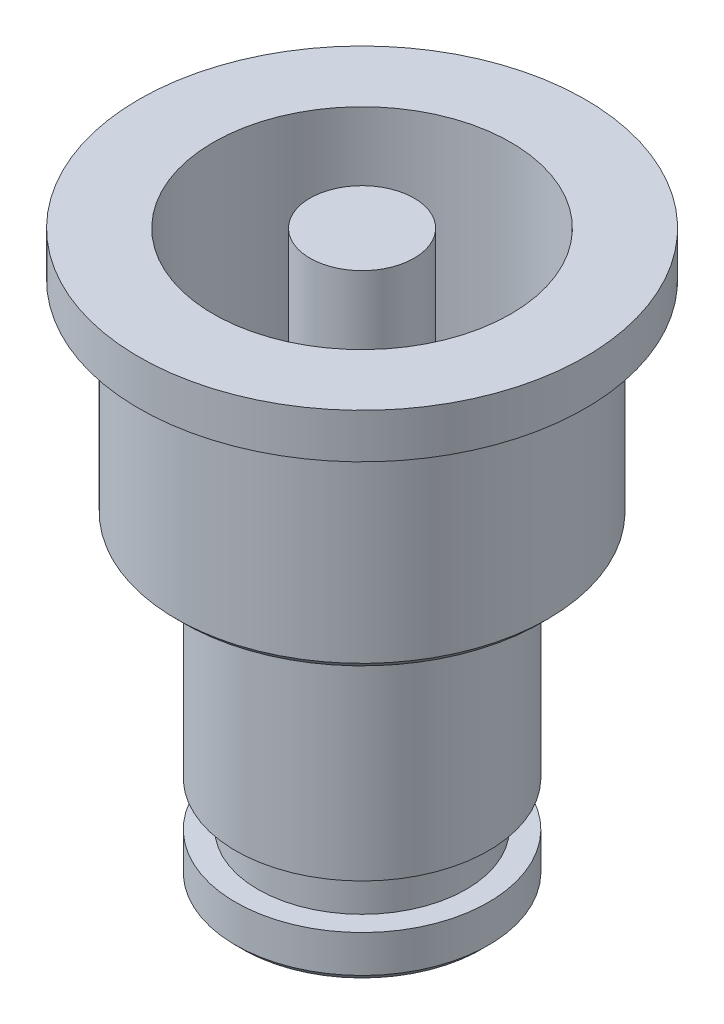
SolidWorks part; units mm, degrees
ref_plane "Plan de face" through (0, 0, 0) normal (0, 0, 1) x (1, 0, 0)
ref_plane "Plan de dessus" through (0, 0, 0) normal (0, 1, 0) x (1, 0, 0)
ref_plane "Plan de droite" through (0, 0, 0) normal (1, 0, 0) x (0, 0, -1)
sketch "Sketch1" plane through (0, 0, 0) normal (0, 1, 0) x (1, 0, 0)
  line L1 (0, 8) -> (-88, 8)
  line L2 (0, 8) -> (0, -8)
  line L3 (0, -8) -> (-88, -8)
  line L4 (-88, 8) -> (-88, -8)
  line L5 (-85, 6.25) -> (-62, 6.25)
  line L6 (-85, 6.25) -> (-85, -6.25)
  line L7 (-85, -6.25) -> (-62, -6.25)
  line L8 (-62, 6.25) -> (-62, -6.25)
  line L9 (-85, 6.25) -> (-62, -6.25) construction
  line L10 (-85, -6.25) -> (-62, 6.25) construction
  point P4 (0, 0)
  point P6 (-73.5, 0)
  dimension "D1" = 88
  dimension "D2" = 16
  dimension "D3" = 3
  dimension "D4" = 23
  dimension "D5" = 12.5
extrude "Boss-Extrude1" add sketch "Sketch1" along normal blind 5
sketch "Sketch2" plane through (0, 0, 0) normal (0, -1, 0) x (1, 0, 0)
  circle A0 centre (0, 0) radius 8
extrude "Boss-Extrude2" add sketch "Sketch2" along normal blind 5 and the other way up to surface (5 mm away) other way up to face at (-44, 5, 0)
fillet "Fillet1" radius 2 1 edges at (-8, 0, 0)
sketch "Sketch11" plane through (0, 0, 0) normal (0, 0, 1) x (1, 0, 0)
  line L0 (0, -5) -> (0, -43) construction
  line L1 (-8, -5) -> (8, -5) construction
  line L2 (0, -5) -> (15, -5)
  line L3 (15, -5) -> (15, -8)
  line L4 (15, -8) -> (12.5, -8)
  line L5 (12.5, -8) -> (12.5, -22)
  line L6 (12.5, -22) -> (8.5, -22)
  line L7 (8.5, -22) -> (8.5, -37)
  line L8 (8.5, -37) -> (7, -37)
  line L9 (7, -37) -> (7, -40)
  line L10 (7, -40) -> (8.5, -40)
  line L11 (8.5, -40) -> (8.5, -43)
  line L12 (8.5, -43) -> (0, -43)
  line L14 (0, -5) -> (0, -43)
  dimension "D1" = 30
  dimension "D2" = 25
  dimension "D3" = 3
  dimension "D4" = 14
  dimension "D5" = 17
  dimension "D6" = 21
  dimension "D7" = 3
  dimension "D8" = 3
  dimension "D9" = 14
  dimension "D10" = 17
revolve "Revolve1" add sketch "Sketch11" angle 360 about L0
chamfer "Chamfer1" distance 0.5 angle 45 2 edges at (-8.5, -43, 0) (-12.5, -22, 0)
sketch "Sketch5" plane through (0, -43, 0) normal (0, -1, 0) x (1, 0, 0)
  line L0 (-1.45, 2.569) -> (-1.45, -2.569)
  line L1 (1.45, 2.569) -> (1.45, -2.569)
  arc A0 (-1.45, -2.569) -> (1.45, -2.569) centre (0, 0) ccw
  arc A1 (1.45, 2.569) -> (-1.45, 2.569) centre (0, 0) ccw
  dimension "D1" = 5.9
  dimension "D2" = 1.45
  dimension "D3" = 1.45
extrude "Cut-Extrude1" cut sketch "Sketch5" against normal blind 8
sketch "Sketch6" plane through (0, 5, 0) normal (0, 1, 0) x (1, 0, 0)
  line L0 (-62, -6.25) -> (-62, 6.25) construction
  line L1 (-62, -3) -> (-59, -3)
  line L2 (-62, -3) -> (-62, 3)
  line L3 (-62, 3) -> (-59, 3)
  line L4 (-59, -3) -> (-59, 3)
  line L7 (-56, 3) -> (-12, 3)
  line L8 (-56, 3) -> (-56, -3)
  line L9 (-56, -3) -> (-12, -3)
  line L10 (-12, 3) -> (-12, -3)
  point P6 (-62, 0)
  point P7 (-62, 0)
  dimension "D1" = 6
  dimension "D2" = 3
  dimension "D3" = 50
  dimension "D4" = 3
extrude "Cut-Extrude2" cut sketch "Sketch6" against normal up to surface (5 mm away) up to face at (-48, 0, 0)
chamfer "Chamfer2" distance 0.5 angle 45 5 edges at (-62, 5, -4.625) (-62, 5, 4.625) (-73.5, 5, 6.25) (-85, 5, 0) (-73.5, 5, -6.25)
shell "Shell1" [suppressed] thickness 2
sketch "Sketch12" plane through (0, 0, 0) normal (0, 0, 1) x (1, 0, 0)
  line L0 (15, -5) -> (-15, -5) construction
  line L1 (9.1233, -5) -> (-100.7586, -5)
  line L2 (9.1233, -5) -> (9.1233, 7.135)
  line L3 (9.1233, 7.135) -> (-100.7586, 7.135)
  line L4 (-100.7586, -5) -> (-100.7586, 7.135)
extrude "Cut-Extrude3" cut sketch "Sketch12" against normal through all both and the other way through all
sketch "Sketch13" plane through (0, -5, 0) normal (0, 1, 0) x (1, 0, 0)
  circle A0 centre (0, 0) radius 10
  circle A2 centre (0, 0) radius 3.5
  dimension "D1" = 20
  dimension "D2" = 7
extrude "Cut-Extrude4" cut sketch "Sketch13" against normal blind 15 and the other way through all contours A0 | A0 region at (-9.7172, -5, 0)
